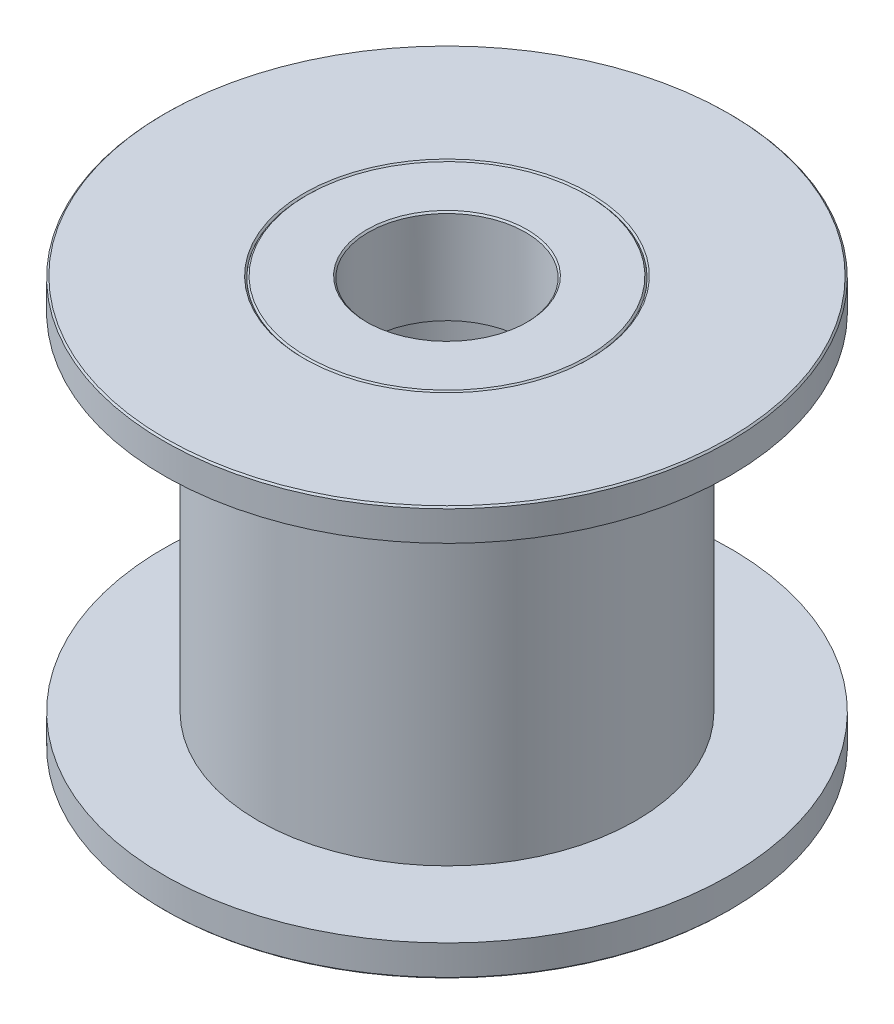
SolidWorks part; units mm, degrees
ref_plane "Front Plane" through (0, 0, 0) normal (0, 0, 1) x (1, 0, 0)
ref_plane "Top Plane" through (0, 0, 0) normal (0, 1, 0) x (1, 0, 0)
ref_plane "Right Plane" through (0, 0, 0) normal (1, 0, 0) x (0, 0, -1)
sketch "Sketch1" plane through (0, 0, 0) normal (0, 0, 1) x (1, 0, 0)
  line L0 (0, -12.8882) -> (0, 12.8882) construction
  line L1 (6, 3.4242) -> (9, 3.4242)
  line L5 (9, 4.4242) -> (9, 3.4242)
  line L9 (4.5, -8.5758) -> (4.5, -5.5758)
  line L16 (4.5, 4.4242) -> (9, 4.4242)
  line L17 (6, -7.5758) -> (6, 3.4242)
  line L18 (6, -7.5758) -> (9, -7.5758)
  line L19 (3.5, -5.5758) -> (3.5, 1.4242)
  line L22 (3.5, 1.4242) -> (4.5, 1.4242)
  line L23 (4.5, 4.4242) -> (4.5, 1.4242)
  line L24 (9, -7.5758) -> (9, -8.5758)
  line L25 (3.5, -5.5758) -> (4.5, -5.5758)
  line L26 (4.5, -8.5758) -> (9, -8.5758)
  line L28 (4.5, 1.4242) -> (2.5, 1.4242)
  line L29 (4.5, 1.4242) -> (4.5, 4.4242)
  line L30 (4.5, 4.4242) -> (2.5, 4.4242)
  line L31 (2.5, 1.4242) -> (2.5, 4.4242)
  line L32 (4.5, -5.5758) -> (2.5, -5.5758)
  line L33 (4.5, -5.5758) -> (4.5, -8.5758)
  line L34 (4.5, -8.5758) -> (2.5, -8.5758)
  line L35 (2.5, -5.5758) -> (2.5, -8.5758)
  point P4 (0, 0)
  dimension "D1" = 13
  dimension "D2" = 1
  dimension "D3" = 3
  dimension "D4" = 1
  dimension "D5" = 3.5
  dimension "D6" = 4.5
  dimension "D7" = 6
  dimension "D8" = 9
  dimension "D9" = 3
  dimension "D10" = 1
  dimension "D11" = 2
  dimension "D12" = 2
revolve "Revolve1" add sketch "Sketch1" angle 360 about L0 region at (5.3962, -2.0758, 0)
chamfer "Chamfer1" distance 0.05 angle 45 4 edges at (4.5, -8.5758, 0) (4.5, 4.4242, 0) (9, 4.4242, 0) (9, -8.5758, 0)
revolve "Revolve2" add sketch "Sketch1<3>" angle 360 about L0 region at (3.5, 2.9242, 0) region at (3.5, -7.0758, 0)
sketch "Sketch1<3>" plane through (0, 0, 0) normal (0, 0, 1) x (1, 0, 0) same geometry as "Sketch1"
chamfer "Chamfer2" distance 0.05 angle 45 2 edges at (4.5, -8.5758, 0) (2.5, -8.5758, 0)
chamfer "Chamfer3" distance 0.05 angle 45 2 edges at (4.5, 4.4242, 0) (2.5, 4.4242, 0)
